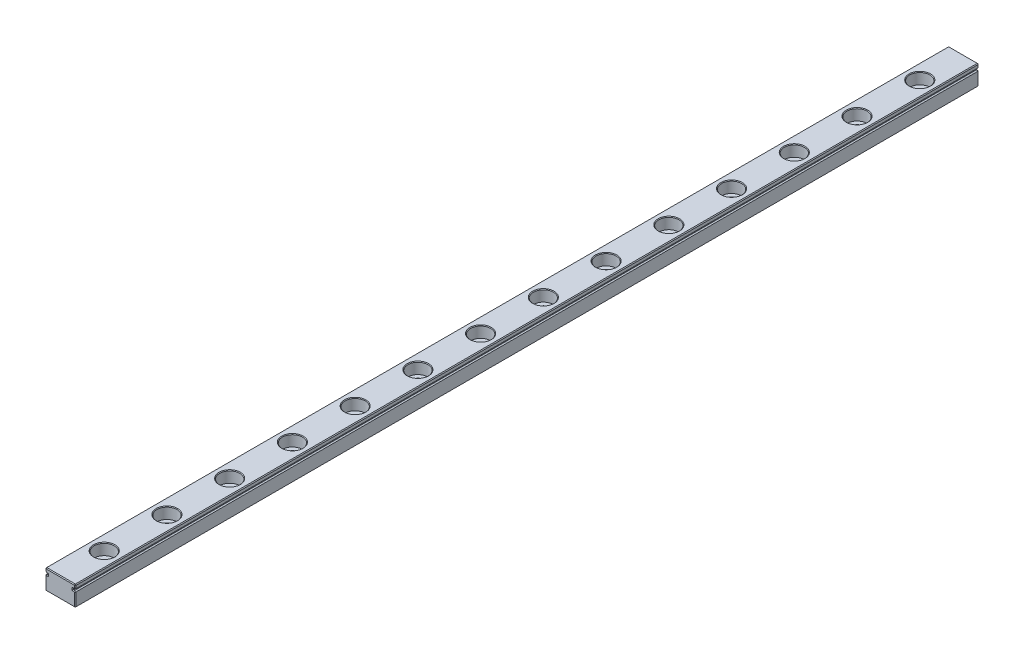
SolidWorks part; units mm, degrees
material "AISI 304"
ref_plane "Front Plane" through (0, 0, 0) normal (0, 0, 1) x (1, 0, 0)
ref_plane "Top Plane" through (0, 0, 0) normal (0, 1, 0) x (1, 0, 0)
ref_plane "Right Plane" through (0, 0, 0) normal (1, 0, 0) x (0, 0, -1)
sketch "Sketch1" plane through (0, 0, 0) normal (0, 0, 1) x (1, 0, 0)
  line L0 (0, 0) -> (0, 8) construction
  line L1 (0, 8) -> (12, 8)
  line L2 (0, 0) -> (12, 0)
  line L3 (0, 8) -> (0, 6.75)
  line L4 (0, 6.75) -> (0.5, 6.25) construction
  line L5 (0.5, 6.25) -> (1, 6.25)
  line L6 (0.5, 5.75) -> (0, 5.25) construction
  line L7 (0, 5.25) -> (0, 0)
  line L8 (1, 6.25) -> (1, 5.75)
  line L9 (1, 5.75) -> (0.5, 5.75)
  line L10 (0.5, 5.75) -> (0.75, 6) construction
  line L11 (0.75, 6) -> (0.5, 6.25) construction
  line L12 (0, 6.75) -> (0, 6.559)
  line L13 (0, 5.25) -> (0, 5.441)
  line L14 (6, 8) -> (6, 0) construction
  line L15 (11.25, 6) -> (11.5, 6.25) construction
  line L16 (11.5, 5.75) -> (11.25, 6) construction
  line L17 (11.5, 5.75) -> (12, 5.25) construction
  line L18 (12, 6.75) -> (11.5, 6.25) construction
  line L19 (12, 0) -> (12, 8) construction
  line L20 (12, 5.25) -> (12, 5.441)
  line L21 (12, 6.75) -> (12, 6.559)
  line L22 (11, 5.75) -> (11.5, 5.75)
  line L23 (11, 6.25) -> (11, 5.75)
  line L24 (12, 5.25) -> (12, 0)
  line L25 (11.5, 6.25) -> (11, 6.25)
  line L26 (12, 8) -> (12, 6.75)
  arc A0 (0, 5.441) -> (0.5, 5.75) centre (0, 6) ccw
  arc A1 (0.5, 6.25) -> (0, 6.559) centre (0, 6) ccw
  arc A2 (11.5, 6.25) -> (12, 6.559) centre (12, 6) cw
  arc A3 (12, 5.441) -> (11.5, 5.75) centre (12, 6) cw
  point P4 (1, 6)
  point P28 (11, 6)
  dimension "D1" = 8
  dimension "D2" = 6
  dimension "D3" = 0.5
  dimension "D4" = 45
  dimension "D5" = 2
  dimension "D6" = 1
extrude "Boss-Extrude1" add sketch "Sketch1" along normal blind 360
chamfer "Chamfer1" distance 0.3 angle 45 36 edges at (0, 0, 180) (12, 0, 180) (0, 8, 180) (12, 8, 180) (0.2939, 5.5245, 360) (0.75, 5.75, 360) (1, 6, 360) (0.75, 6.25, 360) (0.2939, 6.4755, 360) (0, 7.2795, 360) (6, 8, 360) (12, 7.2795, 360) (11.7061, 6.4755, 360) (11.25, 6.25, 360) (11, 6, 360) (11.25, 5.75, 360) (11.7061, 5.5245, 360) (12, 2.7205, 360) (6, 0, 360) (0, 2.7205, 360) (12, 2.7205, 0) (11.7061, 5.5245, 0) (11.25, 5.75, 0) (11, 6, 0) (11.25, 6.25, 0) (11.7061, 6.4755, 0) (12, 7.2795, 0) (6, 0, 0) (0, 2.7205, 0) (0.2939, 5.5245, 0) (0.75, 5.75, 0) (1, 6, 0) (0.75, 6.25, 0) (0.2939, 6.4755, 0) (0, 7.2795, 0) (6, 8, 0)
hole_wizard "CBORE for M5 Hex Head Bolt1" positions "3DSketch1" profile "Sketch3" counterbore size "M5" standard "ANSI Metric" end condition through all
sketch3d "3DSketch1"
  line L0 (6, 8, 0) -> (6, 8, 17.5) construction
  line L1 (11.7, 8, 0) -> (0.3, 8, 0) construction
  point P0 (6, 8, 17.5)
  dimension "D1" = 17.5
sketch "Sketch3" plane through (6, 8, 17.5) normal (1, 0, 0) x (0, 0, 1)
  line L0 (0, 0) -> (0, 8)
  line L1 (2.25, 7.75) -> (2.5, 8)
  line L2 (4, 4.5) -> (2.25, 4.5)
  line L3 (2.25, 4.5) -> (2.25, 7.75)
  line L5 (4, 4.5) -> (4, 0.25)
  line L6 (4, 0.25) -> (4.25, 0)
  line L7 (4.25, 0) -> (0, 0)
  line L8 (-4, 0.25) -> (-4.25, 0) construction
  line L11 (0, -6.35) -> (0, 107.95) construction
  line L12 (2.5, 8) -> (0, 8)
  line L13 (-2.25, 7.75) -> (-2.5, 8) construction
  dimension "Thru Hole Dia." = 4.5
  dimension "Thru Hole Depth" = 8
  dimension "C'Bore Dia." = 8
  dimension "C'Bore Depth" = 4.5
  dimension "Near C'Sink Dia." = 8.5
  dimension "Near C'Sink Angle" = 90
  dimension "Far C'Sink Dia." = 5
  dimension "Far C'Sink Angle" = 90
pattern_linear "LPattern1" count 14 spacing 25 along (0, 0, 1) of "CBORE for M5 Hex Head Bolt1"
